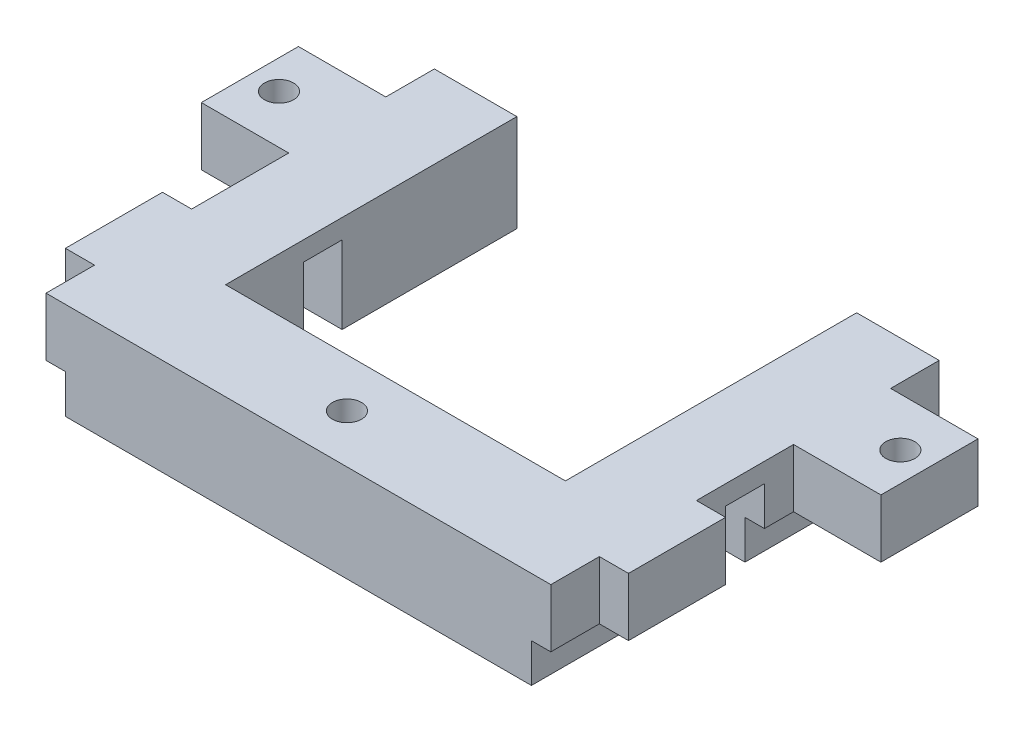
SolidWorks part; units mm, degrees
ref_plane "Front Plane" through (0, 0, 0) normal (0, 0, 1) x (1, 0, 0)
ref_plane "Top Plane" through (0, 0, 0) normal (0, 1, 0) x (1, 0, 0)
ref_plane "Right Plane" through (0, 0, 0) normal (1, 0, 0) x (0, 0, -1)
sketch "Sketch1" plane through (0, 0, 0) normal (0, 0, 1) x (1, 0, 0)
  line L0 (24, -3) -> (29, -3)
  line L1 (-24, -7) -> (24, -7)
  line L2 (-24, -7) -> (-24, -3)
  line L4 (24, -7) -> (24, -3)
  line L5 (-29, -3) -> (-24, -3)
  line L6 (-29, -3) -> (-29, 3)
  line L7 (-29, 3) -> (29, 3)
  line L8 (29, -3) -> (29, 3)
  line L9 (-29, 3) -> (29, -3) construction
  line L10 (0, -7) -> (0, 0) construction
  dimension "D1" = 10
  dimension "D2" = 48
  dimension "D3" = 5
  dimension "D4" = 4
extrude "Boss-Extrude1" add sketch "Sketch1" along normal blind 40
sketch "Sketch2" plane through (0, 3, 0) normal (0, 1, 0) x (1, 0, 0)
  line L0 (0, 0) -> (0, -15) construction
  line L1 (-17.5, 0) -> (17.5, 0)
  line L2 (-17.5, 0) -> (-17.5, -30)
  line L3 (-17.5, -30) -> (17.5, -30)
  line L4 (17.5, 0) -> (17.5, -30)
  line L5 (-17.5, 0) -> (17.5, -30) construction
  line L6 (-17.5, -30) -> (17.5, 0) construction
  line L7 (29, 0) -> (-29, 0) construction
  line L8 (29, -40) -> (29, 0) construction
  line L9 (26, -25) -> (29, -25)
  line L10 (26, -25) -> (26, -15)
  line L11 (26, -15) -> (29, -15)
  line L12 (29, -25) -> (29, -15)
  line L13 (-29, -25) -> (-26, -25)
  line L17 (35, -5) -> (26, -5) construction
  line L18 (26, -15) -> (35, -15) construction
  line L19 (26, -35) -> (29, -35) construction
  line L20 (29, -40) -> (26, -40)
  line L21 (29, -40) -> (29, -35)
  line L22 (29, -35) -> (26, -35)
  line L23 (26, -40) -> (26, -35)
  line L24 (-29, -40) -> (-26, -40)
  line L25 (-29, -40) -> (-29, -35)
  line L26 (-29, -25) -> (-29, -15)
  line L27 (-29, -15) -> (-26, -15)
  line L28 (-26, -25) -> (-26, -15)
  line L29 (-84, -25) -> (-81, -25)
  line L30 (-84, -25) -> (-84, -15)
  line L31 (-84, -15) -> (-81, -15)
  line L32 (-81, -25) -> (-81, -15)
  line L33 (26, -5) -> (29, -5)
  line L34 (26, -5) -> (26, 5)
  line L35 (26, 5) -> (29, 5)
  line L36 (29, -5) -> (29, 5)
  line L37 (-29, -5) -> (-26, -5)
  line L38 (-29, -5) -> (-29, 5)
  line L39 (-29, 5) -> (-26, 5)
  line L40 (-26, -5) -> (-26, 5)
  line L41 (-84, -5) -> (-81, -5)
  line L42 (-84, -5) -> (-84, 5)
  line L43 (-84, 5) -> (-81, 5)
  line L44 (-81, -5) -> (-81, 5)
  line L45 (-29, -35) -> (-26, -35)
  line L46 (-26, -40) -> (-26, -35)
  point P0 (0, -15)
  dimension "D1" = 30
  dimension "D2" = 35
  dimension "D4" = 3
  dimension "D5" = 10
  dimension "D6" = 3
  dimension "D7" = 2
extrude "Cut-Extrude1" cut sketch "Sketch2" against normal through all
sketch "Sketch3" plane through (0, -7, 0) normal (0, -1, 0) x (1, 0, 0)
  line L0 (29, 15) -> (29, 5) construction
  line L1 (29, 18) -> (-29, 18)
  line L2 (29, 18) -> (29, 22)
  line L3 (29, 22) -> (-29, 22)
  line L4 (-29, 18) -> (-29, 22)
  line L5 (29, 18) -> (-29, 22) construction
  line L6 (29, 22) -> (-29, 18) construction
  line L7 (17.5, 0) -> (24, 0) construction
  point P0 (0, 20)
  dimension "D1" = 4
  dimension "D2" = 20
extrude "Cut-Extrude2" cut sketch "Sketch3" against normal blind 8
sketch "Sketch4" plane through (0, 0, 0) normal (0, 1, 0) x (1, 0, 0)
  line L0 (29, -15) -> (35, -5) construction
  line L1 (29, -15) -> (35, -15)
  line L2 (29, -15) -> (29, -5)
  line L3 (29, -5) -> (35, -5)
  line L4 (35, -15) -> (35, -5)
  line L5 (35, -5) -> (35.0892, -4.9108) construction
  line L6 (26, -5) -> (29, -5) construction
  circle A0 centre (32, -10) radius 1.5
  dimension "D2" = 3
  dimension "D1" = 6
extrude "Boss-Extrude2" add sketch "Sketch4" along normal blind 3 and the other way blind 3
mirror "Mirror1" about plane through (0, 0, 0) normal (1, 0, 0) of "Boss-Extrude2"
sketch "Sketch5" plane through (0, 3, 0) normal (0, 1, 0) x (1, 0, 0)
  line L0 (17.5, -30) -> (-17.5, -40) construction
  line L1 (26, -40) -> (-26, -40) construction
  circle A0 centre (0, -35) radius 1.5
  dimension "D1" = 3
extrude "Cut-Extrude3" cut sketch "Sketch5" against normal blind 10
